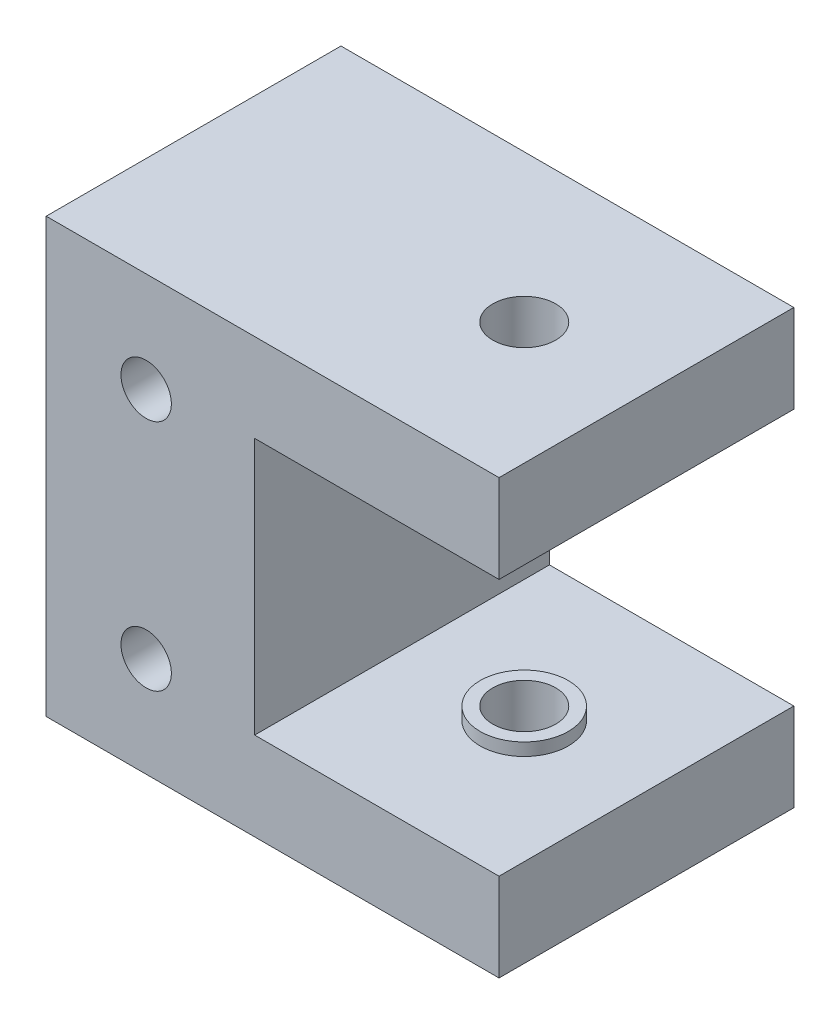
SolidWorks part; units mm, degrees
ref_plane "Front Plane" through (0, 0, 0) normal (0, 0, 1) x (1, 0, 0)
ref_plane "Top Plane" through (0, 0, 0) normal (0, 1, 0) x (1, 0, 0)
ref_plane "Right Plane" through (0, 0, 0) normal (1, 0, 0) x (0, 0, -1)
sketch "MainBlock" plane through (0, 0, 0) normal (0, 0, 1) x (1, 0, 0)
  line L0 (0, 0) -> (35.95, 0)
  line L1 (35.95, 0) -> (35.95, 7)
  line L2 (35.95, 7) -> (16.55, 7)
  line L3 (16.55, 7) -> (16.55, 27.4)
  line L4 (16.55, 27.4) -> (35.95, 27.4)
  line L5 (35.95, 27.4) -> (35.95, 34.4)
  line L6 (35.95, 34.4) -> (0, 34.4)
  line L7 (0, 34.4) -> (0, 0)
  circle A0 centre (7.9375, 26.4625) radius 2
  circle A1 centre (7.9375, 7.9375) radius 2
  dimension "D4" = 4
  dimension "D1" = 35.95
  dimension "D2" = 34.4
  dimension "D3" = 20.4
  dimension "D5" = 19.4
  dimension "D6" = 7.9375
  dimension "D7" = 7.9375
  dimension "D8" = 7.9375
extrude "MainBlockBoss-Extrude1" add sketch "MainBlock" along normal blind 23.4
sketch "TopHoleCut-Sketch2" plane through (0, 34.4, 0) normal (0, 1, 0) x (1, 0, 0)
  line L0 (35.95, 0) -> (0, 0) construction
  line L1 (0, -23.4) -> (0, 0) construction
  circle A0 centre (26.25, -11.7) radius 2.5
  dimension "D3" = 5
  dimension "D1" = 11.7
  dimension "D2" = 26.25
extrude "TopHoleCut-Extrude1" cut sketch "TopHoleCut-Sketch2" against normal blind 30
sketch "TopSpacerSketch4" plane through (0, 27.4, 0) normal (0, -1, 0) x (1, 0, 0)
  circle A0 centre (26.25, 11.7) radius 3.5
  circle A1 centre (26.25, 11.7) radius 2.5
  circle A2 centre (26.25, 11.7) radius 2.5 construction
  dimension "D1" = 7
extrude "TopSpacerBoss-Extrude2" add sketch "TopSpacerSketch4" along normal blind 1
sketch "LowerSpacerSketch5" plane through (0, 7, 0) normal (0, 1, 0) x (1, 0, 0)
  circle A0 centre (26.25, -11.7) radius 2.5
  circle A1 centre (26.25, -11.7) radius 2.5 construction
  circle A2 centre (26.25, -11.7) radius 3.5
  circle A3 centre (26.25, -11.7) radius 3.5 construction
extrude "LowerSpacerBoss-Extrude3" add sketch "LowerSpacerSketch5" along normal blind 1
sketch "MountHoleBoreSketch1" plane through (0, 0, 0) normal (0, 0, -1) x (-1, 0, 0)
  line L1 (-4.0625, 26.4625) -> (-6, 29.8183)
  line L2 (-6, 29.8183) -> (-9.875, 29.8183)
  line L3 (-9.875, 29.8183) -> (-11.8125, 26.4625)
  line L4 (-11.8125, 26.4625) -> (-9.875, 23.1067)
  line L5 (-9.875, 23.1067) -> (-6, 23.1067)
  line L6 (-6, 23.1067) -> (-4.0625, 26.4625)
  line L7 (-4.0625, 7.9375) -> (-6, 11.2933)
  line L8 (-6, 11.2933) -> (-9.875, 11.2933)
  line L9 (-9.875, 11.2933) -> (-11.8125, 7.9375)
  line L10 (-11.8125, 7.9375) -> (-9.875, 4.5817)
  line L11 (-9.875, 4.5817) -> (-6, 4.5817)
  line L12 (-6, 4.5817) -> (-4.0625, 7.9375)
  circle A0 centre (-7.9375, 26.4625) radius 3.3558 construction
  circle A1 centre (-7.9375, 7.9375) radius 3.3558 construction
  dimension "D1" = 7.75
extrude "MountHoleBoreCut-Extrude1" cut sketch "MountHoleBoreSketch1" against normal blind 2
sketch "PushPinHoleSketch1" plane through (0, 0, 0) normal (0, -1, 0) x (1, 0, 0)
  circle A0 centre (26.25, 11.7) radius 1
  circle A1 centre (26.25, 11.7) radius 2.5 construction
  dimension "D1" = 2
extrude "PushPinHoleCut-Extrude1" cut sketch "PushPinHoleSketch1" against normal through all
equation "\"BeltTensionerWidth\"= \"MidRailToAlignWithGantryBlock\" + \"BeltTensionerInnerWidth\" / 2"
equation "\"BeltTensionerHeight\"= \"BeltTensionerInnerHeight\" + \"BeltTensionerUpperLowerWallThickness\" * 2"
equation "\"BeltTensionerDepth\"= \"BeltTensionerBackWallThickness\" + \"BeltTensionerInnerDepth\"'Equals 23.4"
equation "\"BeltTensionerUpperLowerWallThickness\"= 7mm"
equation "\"BeltTensionerInnerWidth\"= \"20TGT2PulleyDiameter\" + \"BeltTensionerSpaceBetweenPulleyAndWall\""
equation "\"BeltTensionerInnerHeight\"= \"20TGT2PulleyWidth\" * 2 + \"1mmSpacer\" * 3"
equation "\"BeltTensionerBackWallThickness\"= 4mm"
equation "\"BeltTensionerInnerDepth\"= \"20TGT2PulleyDiameter\" + \"BeltTensionerSpaceBetweenPulleyAndWall\""
equation "\"RailThickness\"= .125in'Spec"
equation "\"HoleOffsetFromEdge\"= \"RailThickness\" * 2.5"
equation "\"LinearGBWithRailDepth\"= 12.75mm'Spec"
equation "\"GABDistanceFromBackToFirstPulley\"= 13.5mm"
equation "\"MidRailToAlignWithGantryBlock\"= \"LinearGBWithRailDepth\" + \"GABDistanceFromBackToFirstPulley\"'All outside cogs must align"
equation "\"20TGT2PulleyDiameter\"= 17.9mm'Spec"
equation "\"BeltTensionerSpaceBetweenPulleyAndWall\"= 1.5mm"
equation "\"BeltTensionerMountingHoleDiameter\"= 4.0mm"
equation "\"BeltTensionerMountingHoleOffsetFromEdge\"= \"HoleOffsetFromEdge\""
equation "\"20TGT2PulleyWidth\"= 8.7mm'The STL of the Pulley in the diagram is a bit larger"
equation "\"1mmSpacer\"= 1mm"
equation "\"SteelShaft5mmHoleDiameter\"= 5mm"
equation "\"BeltTensionerMountingHoleOuterBoreDepth\"= 2mm"
equation "\"BeltTensionerMountingHoleOuterBoreDiameter\"= 7.75mm"
equation "\"7mmx1mmSpacerDiameter\"= 7mm"
equation "\"7mmx1mmSpacerHeight\"= 1mm"
equation "\"D1@MainBlock\" = \"BeltTensionerWidth\""
equation "\"D2@MainBlock\" = \"BeltTensionerHeight\""
equation "\"D3@MainBlock\" = \"BeltTensionerInnerHeight\""
equation "\"D4@MainBlock\" = \"BeltTensionerMountingHoleDiameter\""
equation "\"D5@MainBlock\" = \"BeltTensionerInnerWidth\""
equation "\"D6@MainBlock\"=\"BeltTensionerMountingHoleOffsetFromEdge\""
equation "\"D7@MainBlock\" = \"HoleOffsetFromEdge\""
equation "\"D8@MainBlock\" = \"HoleOffsetFromEdge\""
equation "\"D1@MainBlockBoss-Extrude1\" = \"BeltTensionerDepth\""
equation "\"D1@TopHoleCut-Sketch2\" = \"BeltTensionerDepth\" / 2"
equation "\"D2@TopHoleCut-Sketch2\" = \"MidRailToAlignWithGantryBlock\""
equation "\"D3@TopHoleCut-Sketch2\" = \"SteelShaft5mmHoleDiameter\""
equation "\"D1@TopSpacerSketch4\" = \"7mmx1mmSpacerDiameter\""
equation "\"D1@TopSpacerBoss-Extrude2\" = \"7mmx1mmSpacerHeight\""
equation "\"D1@LowerSpacerBoss-Extrude3\" = \"7mmx1mmSpacerHeight\""
equation "\"D1@MountHoleBoreSketch1\" = \"BeltTensionerMountingHoleOuterBoreDiameter\""
equation "\"D1@MountHoleBoreCut-Extrude1\" = \"BeltTensionerMountingHoleOuterBoreDepth\""
equation "\"StealPinPushHoleDiameter\"= 2mm"
equation "\"D1@PushPinHoleSketch1\" = \"StealPinPushHoleDiameter\""
